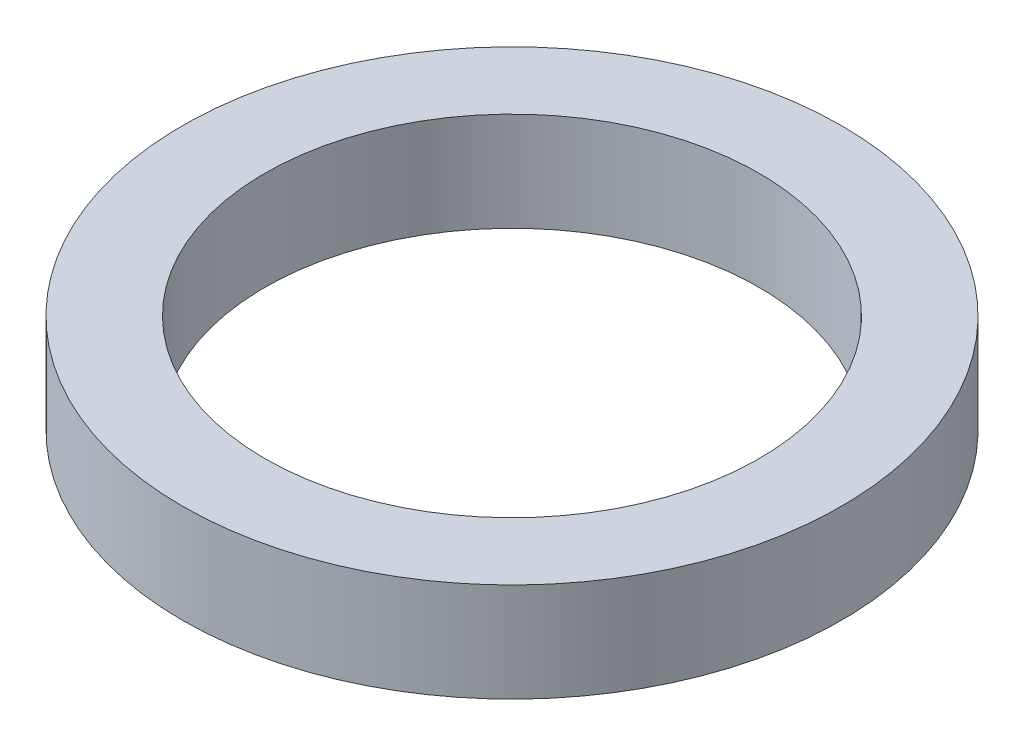
SolidWorks part; units mm, degrees
ref_plane "Front Plane" through (0, 0, 0) normal (0, 0, 1) x (1, 0, 0)
ref_plane "Top Plane" through (0, 0, 0) normal (0, 1, 0) x (1, 0, 0)
ref_plane "Right Plane" through (0, 0, 0) normal (1, 0, 0) x (0, 0, -1)
sketch "Sketch1" plane through (0, 0, 0) normal (0, 1, 0) x (1, 0, 0)
  circle A0 centre (0, 0) radius 60
  dimension "FLANGE_OD" = 120
extrude "Boss-Extrude1" add sketch "Sketch1" along normal blind 18
sketch "Sketch2" plane through (0, 0, 0) normal (0, 1, 0) x (1, 0, 0)
  circle A0 centre (0, 0) radius 45
  dimension "BORE_D" = 90
extrude "Cut-Extrude1" cut sketch "Sketch2" along normal through all
sketch "Sketch3" plane through (0, 18, 0) normal (0, 1, 0) x (1, 0, 0)
  circle A0 centre (0, 0) radius 25.6219 construction
  circle A1 centre (-25.6219, 0) radius 2.2262
  dimension "BOLT_D" = 4.4523
  dimension "BOLT_PCD" = 51.2438
extrude "Cut-Extrude2" cut sketch "Sketch3" against normal blind 13.3532 rebuild error yes
pattern_circular "CirPattern1" count 6 over 360 rebuild error yes
